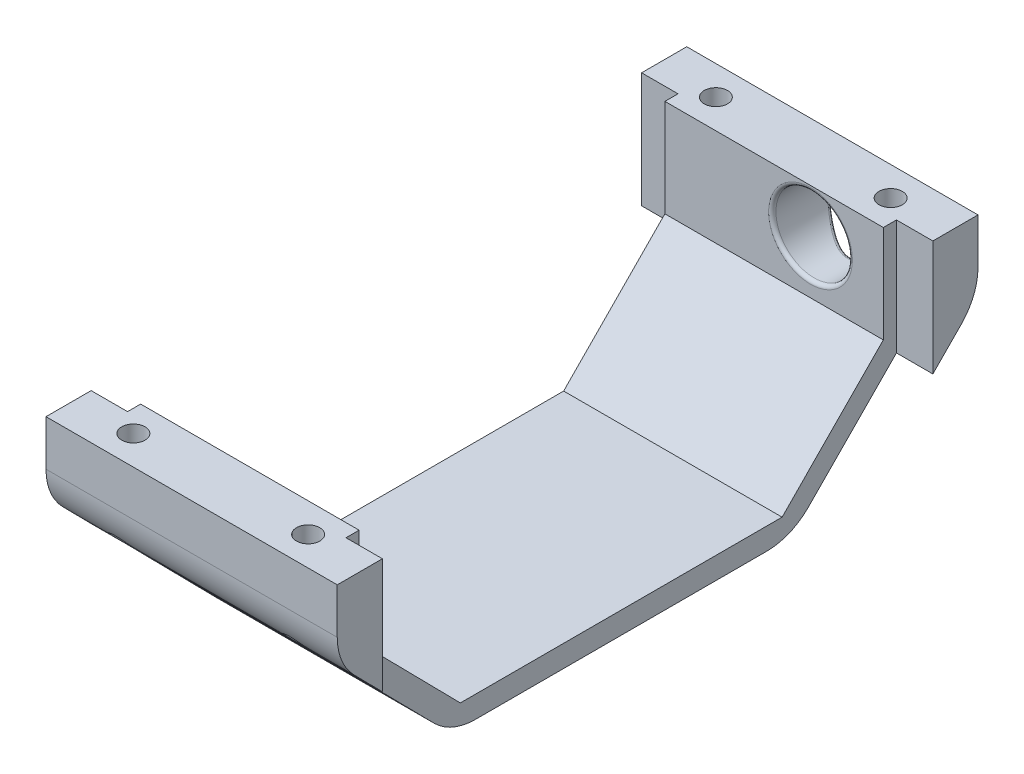
SolidWorks part; units mm, degrees
ref_plane "Alzado" through (0, 0, 0) normal (0, 0, 1) x (1, 0, 0)
ref_plane "Planta" through (0, 0, 0) normal (0, 1, 0) x (1, 0, 0)
ref_plane "Vista lateral" through (0, 0, 0) normal (1, 0, 0) x (0, 0, -1)
sketch "Croquis1" plane through (0, 0, 0) normal (0, 1, 0) x (1, 0, 0)
  line L0 (0, 0) -> (0, 50000) construction
  line L1 (-20, 44) -> (20, 44)
  line L2 (-20, 44) -> (-20, -44)
  line L3 (-20, -44) -> (20, -44)
  line L4 (20, 44) -> (20, -44)
  line L5 (-20, 44) -> (20, -44) construction
  line L6 (-20, -44) -> (20, 44) construction
  line L7 (0, 0) -> (50000, 0) construction
  circle A0 centre (-12, 40) radius 1.6
  circle A1 centre (12, 40) radius 1.6
  circle A2 centre (-12, -40) radius 1.6
  circle A3 centre (12, -40) radius 1.6
  point P0 (0, 0)
  dimension "D4" = 3.2
  dimension "D1" = 40
  dimension "D2" = 88
  dimension "D3" = 24
  dimension "D5" = 4
extrude "Saliente-Extruir1" add sketch "Croquis1" along normal blind 30.5
sketch "Croquis2" plane through (0, 30.5, 0) normal (0, 1, 0) x (1, 0, 0)
  line L0 (20, -44) -> (20, 44) construction
  line L1 (-13, 24) -> (10.2, 24) construction
  line L2 (-13, 24) -> (-13, -27.4) construction
  line L3 (-13, -27.4) -> (10.2, -27.4) construction
  line L4 (10.2, 24) -> (10.2, -27.4) construction
  line L5 (-13, 24) -> (10.2, -27.4) construction
  line L6 (-13, -27.4) -> (10.2, 24) construction
  line L7 (0.6, 54.7934) -> (9.4, 54.7934) construction
  line L8 (0.6, 54.7934) -> (0.6, 9.4014) construction
  line L9 (0.6, 9.4014) -> (9.4, 9.4014) construction
  line L10 (9.4, 54.7934) -> (9.4, 9.4014) construction
  line L11 (0.6, 54.7934) -> (9.4, 9.4014) construction
  line L12 (0.6, 9.4014) -> (9.4, 54.7934) construction
  line L13 (20, 44) -> (-20, 44) construction
  point P4 (-1.4, -1.7)
  point P9 (5, 32.0974)
  dimension "D1" = 51.4
  dimension "D2" = 23.2
  dimension "D3" = 0.8
  dimension "D4" = 8.8
  dimension "D5" = 15
  dimension "D6" = 20
sketch "Croquis3" plane through (0, 30.5, 0) normal (0, 1, 0) x (1, 0, 0)
  line L0 (-20, 44) -> (-20, -44) construction
  line L1 (-20, 37) -> (20, 37)
  line L2 (-20, 37) -> (-20, -37)
  line L3 (-20, -37) -> (20, -37)
  line L4 (20, 37) -> (20, -37)
  line L5 (-20, 37) -> (20, -37) construction
  line L6 (-20, -37) -> (20, 37) construction
  line L7 (20, -44) -> (20, 44) construction
  line L8 (20, 44) -> (-20, 44) construction
  point P4 (0, 0)
  dimension "D1" = 7
ref_plane "Plano1" through (-1.4, 0, 0) normal (1, 0, 0) x (0, 0, -1)
sketch "Croquis7" plane through (0, 0, -44) normal (0, 0, -1) x (-1, 0, 0)
  line L2 (14.1255, 29.1561) -> (7.3275, 29.1561) construction
  line L3 (14.1255, 29.1561) -> (14.1255, 24.9647) construction
  line L4 (14.1255, 24.9647) -> (7.3275, 24.9647) construction
  line L5 (7.3275, 29.1561) -> (7.3275, 24.9647) construction
  line L6 (14.1255, 29.1561) -> (7.3275, 24.9647) construction
  line L7 (14.1255, 24.9647) -> (7.3275, 29.1561) construction
  text T0 "12V"
  point P0 (14.1255, 29.1561)
  point P8 (10.7265, 27.0604)
extrude "Cortar-Extruir4" cut sketch "Croquis7" against normal blind 1
sketch "Croquis8" plane through (0, 0, 0) normal (0, -1, 0) x (1, 0, 0)
  circle A0 centre (-12, 40) radius 2.5
  circle A1 centre (12, 40) radius 2.5
  circle A2 centre (-12, -40) radius 2.5
  circle A3 centre (12, -40) radius 2.5
  dimension "D1" = 5
extrude "Cortar-Extruir5" cut sketch "Croquis8" against normal offset from surface (20.5 mm away) 10 up to face at (-12, 30.5, 38.4)
sketch "Croquis9" plane through (20, 0, 0) normal (1, 0, 0) x (0, 0, -1)
  line L0 (0, 0) -> (0, 50000) construction
  line L1 (20, 0) -> (-20, 0)
  line L2 (-44, 0) -> (44, 0) construction
  line L3 (-25.7009, 2.3876) -> (-41.7009, 18.6399)
  line L4 (-44, 30.5) -> (-44, 0) construction
  line L5 (-44, 24.2523) -> (-44, 30.5)
  line L6 (-44, 30.5) -> (44, 30.5)
  line L8 (44, 24.2523) -> (44, 30.5)
  line L9 (25.7009, 2.3876) -> (41.7009, 18.6399)
  arc A0 (-20, 0) -> (-25.7009, 2.3876) centre (-20, 8) cw
  arc A1 (-41.7009, 18.6399) -> (-44, 24.2523) centre (-36, 24.2523) cw
  arc A2 (41.7009, 18.6399) -> (44, 24.2523) centre (36, 24.2523) ccw
  arc A3 (20, 0) -> (25.7009, 2.3876) centre (20, 8) ccw
  point P17 (0, 0)
  point P25 (0, 30.5)
  dimension "D2" = 8
  dimension "D3" = 8
  dimension "D1" = 40
extrude "Cortar-Extruir6" cut sketch "Croquis9" against normal through all flip side to cut
sketch "Croquis11" plane through (20, 0, 0) normal (1, 0, 0) x (0, 0, -1)
  line L0 (-36, 30.5) -> (-36, 17.1253)
  line L1 (-44, 30.5) -> (44, 30.5) construction
  line L2 (-36, 17.1253) -> (-22.094, 3)
  line L3 (-22.094, 3) -> (22.094, 3)
  line L4 (22.094, 3) -> (36, 17.1253)
  line L5 (36, 17.1253) -> (36, 30.5)
  line L6 (34.2173, 30.5) -> (-34.8586, 30.5) construction
  line L7 (0, 0) -> (0, 26.6558) construction
  line L10 (-41.7009, 18.6399) -> (-25.7009, 2.3876) construction
  line L11 (-20, 0) -> (20, 0) construction
  line L12 (-37.5, 14.3727) -> (-37.5, 20.5) construction
  point P11 (0, 3)
  dimension "D1" = 3
  dimension "D2" = 3
  dimension "D3" = 1.5
extrude "Cortar-Extruir7" cut sketch "Croquis11" against normal through all and the other way through all
sketch "Croquis6" plane through (0, 0, -44) normal (0, 0, -1) x (-1, 0, 0)
  line L1 (-20, 30.5) -> (20, 30.5) construction
  circle A0 centre (-5, 24.5) radius 5.25
  dimension "D2" = 10.5
  dimension "D1" = 6
extrude "Cortar-Extruir3" cut sketch "Croquis6" against normal up to next
fillet "Redondeo1" radius 0.5 3 edges at (10.25, 24.5, -36) (5, 29.75, -44) (5.0823, 19.2506, -42.2437)
sketch "Croquis13" plane through (0, 0, 0) normal (0, -1, 0) x (1, 0, 0)
  line L0 (20, -25.7009) -> (20, -41.7009) construction
  line L1 (20, -37.8) -> (15, -37.8)
  line L2 (20, -37.8) -> (20, 37.8)
  line L3 (20, 37.8) -> (15, 37.8)
  line L4 (15, -37.8) -> (15, 37.8)
  line L5 (0, 0) -> (74.498, 0) construction
  line L6 (0, -16.775) -> (0, 16.775) construction
  line L7 (-20, -37.8) -> (-20, 37.8)
  line L8 (-20, -37.8) -> (-15, -37.8)
  line L9 (-20, 37.8) -> (-15, 37.8)
  line L10 (-15, -37.8) -> (-15, 37.8)
  dimension "D1" = 75.6
  dimension "D2" = 5
extrude "Cortar-Extruir8" cut sketch "Croquis13" against normal through all
